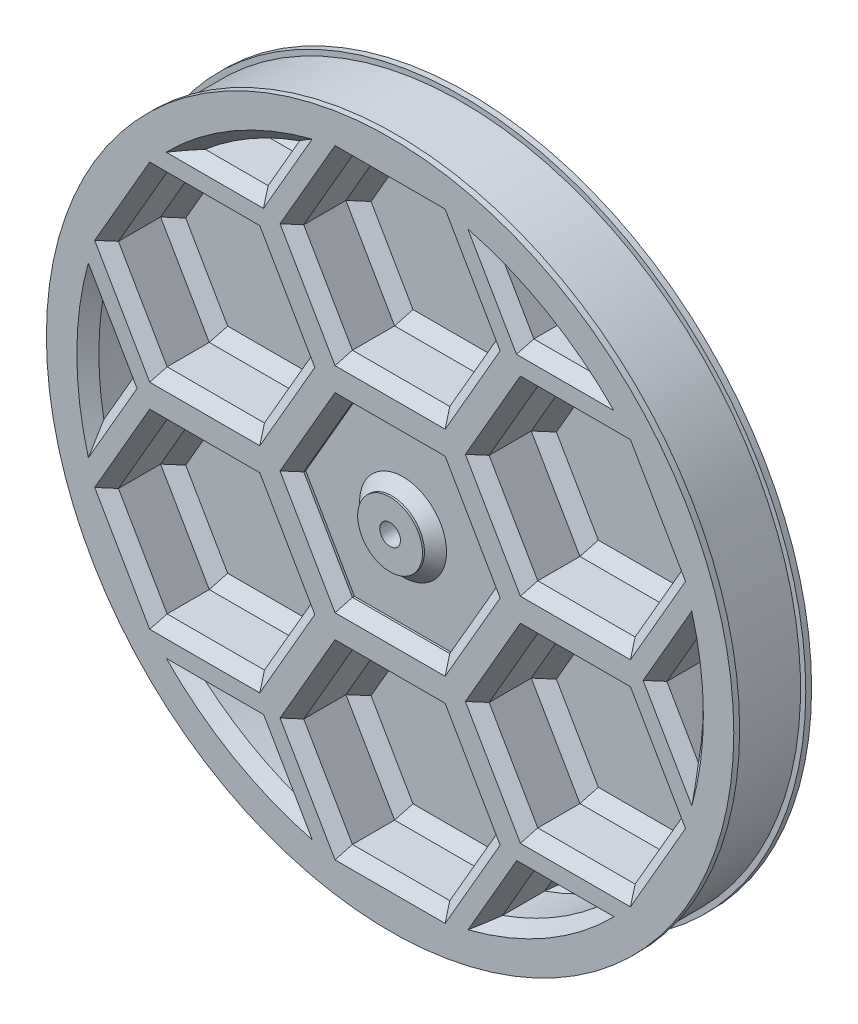
SolidWorks part; units mm, degrees
ref_plane "Front Plane" through (0, 0, 0) normal (0, 0, 1) x (1, 0, 0)
ref_plane "Top Plane" through (0, 0, 0) normal (0, 1, 0) x (1, 0, 0)
ref_plane "Right Plane" through (0, 0, 0) normal (1, 0, 0) x (0, 0, -1)
sketch "Sketch1" plane through (0, 0, 0) normal (0, 0, 1) x (1, 0, 0)
  circle A0 centre (0, 0) radius 33.655
  circle A1 centre (0, 0) radius 1.016
  dimension "D1" = 67.31
  dimension "D2" = 2.032
extrude "Boss-Extrude1" add sketch "Sketch1" along normal blind 7.62 contours A0 A1
sketch "Sketch2" plane through (0, 0, 7.62) normal (0, 0, 1) x (1, 0, 0)
  line L1 (9.5321, 20.955) -> (4.766, 29.21)
  line L2 (4.766, 29.21) -> (-4.766, 29.21)
  line L3 (-4.766, 29.21) -> (-9.5321, 20.955)
  line L4 (-9.5321, 20.955) -> (-4.766, 12.7)
  line L5 (-4.766, 12.7) -> (4.766, 12.7)
  line L6 (4.766, 12.7) -> (9.5321, 20.955)
  line L7 (-8.2562, 30.7849) -> (-13.0222, 39.0399)
  line L8 (-13.0222, 39.0399) -> (-22.5542, 39.0399)
  line L9 (-22.5542, 39.0399) -> (-27.3203, 30.7849)
  line L10 (-27.3203, 30.7849) -> (-22.5542, 22.5299)
  line L11 (-22.5542, 22.5299) -> (-13.0222, 22.5299)
  line L12 (-13.0222, 22.5299) -> (-8.2562, 30.7849)
  line L13 (-8.2416, 11.0999) -> (-13.0077, 19.3549) construction
  line L14 (-13.0077, 19.3549) -> (-22.5397, 19.3549) construction
  line L15 (-22.5397, 19.3549) -> (-27.3057, 11.0999) construction
  line L16 (-27.3057, 11.0999) -> (-22.5397, 2.8449) construction
  line L17 (-22.5397, 2.8449) -> (-13.0077, 2.8449) construction
  line L18 (-13.0077, 2.8449) -> (-8.2416, 11.0999) construction
  circle A0 centre (0, 0) radius 20.955 construction
  circle A1 centre (0, 20.955) radius 8.255 construction
  circle A2 centre (0, 20.955) radius 8.255 construction
  circle A3 centre (0, 0) radius 29.5963
  circle A4 centre (-17.7882, 30.7849) radius 8.255 construction
  circle A6 centre (-17.7737, 11.0999) radius 8.255 construction
  dimension "D1" = 41.91
  dimension "D2" = 16.51
  dimension "D3" = 3.81
  dimension "D4" = 3.81
  dimension "D5" = 3.175
extrude "Cut-Extrude1" cut sketch "Sketch2" against normal blind 6.35 contours L5 L6 L1 L2 L3 L4 | L12 A3 L11
pattern_circular "CirPattern1" count 6 over 360 about axis through (0, 0, 0) along (0, 0, 1) of "Cut-Extrude1"
sketch "Sketch3" plane through (0, 0, 7.62) normal (0, 0, 1) x (1, 0, 0)
  line L1 (9.5321, 0) -> (4.766, 8.255)
  line L2 (4.766, 8.255) -> (-4.766, 8.255)
  line L3 (-4.766, 8.255) -> (-9.5321, 0)
  line L4 (-9.5321, 0) -> (-4.766, -8.255)
  line L5 (-4.766, -8.255) -> (4.766, -8.255)
  line L6 (4.766, -8.255) -> (9.5321, 0)
  circle A0 centre (0, 0) radius 8.255 construction
  circle A1 centre (0, 0) radius 3.175
  dimension "D1" = 16.51
  dimension "D2" = 6.35
extrude "Cut-Extrude2" cut sketch "Sketch3" against normal blind 1.27
sketch "Sketch4" plane through (0, 0, 0) normal (1, 0, 0) x (0, 0, -1)
  line L0 (0, 33.655) -> (-7.62, 33.655) construction
  line L1 (-7.0485, 33.655) -> (-0.5715, 33.655)
  line L2 (-7.0485, 33.655) -> (-7.0485, 33.147)
  line L3 (-7.0485, 33.147) -> (-0.5715, 33.147)
  line L4 (-0.5715, 33.655) -> (-0.5715, 33.147)
  line L5 (-7.0485, 33.655) -> (-0.5715, 33.147) construction
  line L6 (-7.0485, 33.147) -> (-0.5715, 33.655) construction
  line L7 (0, 33.655) -> (-7.62, 33.655) construction
  point P4 (-3.81, 33.401)
  point P9 (-3.81, 33.655)
  dimension "D1" = 6.477
  dimension "D2" = 0.508
sketch "Sketch5" plane through (0, 0, 0) normal (1, 0, 0) x (0, 0, -1)
  line L0 (0, 0) -> (-29.2934, 0) construction
  line L1 (0, -33.655) -> (0, 33.655) construction
revolve "Cut-Revolve1" cut sketch "Sketch4" angle 360 about L0
chamfer "Chamfer1" distance 1.0795 angle 45 62 edges at (33.655, 0, 7.62) (-14.8065, 25.6263, 7.62) (-16.1072, 22.5299, 7.62) (-11.4779, 25.2047, 7.62) (7.149, 16.8275, 7.62) (7.149, 25.0825, 7.62) (0, 29.21, 7.62) (-7.149, 25.0825, 7.62) (-7.149, 16.8275, 7.62) (0, 12.7, 7.62) (-10.9985, 14.605, 7.62) (-18.1476, 18.7325, 7.62) (-25.2966, 14.605, 7.62) (-25.2966, 6.35, 7.62) (-18.1476, 2.2225, 7.62) (-10.9985, 6.35, 7.62) (14.8065, -25.6263, 7.62) (16.1072, -22.5299, 7.62) (11.4779, -25.2047, 7.62) (10.9985, -14.605, 7.62) (18.1476, -18.7325, 7.62) (25.2966, -14.605, 7.62) (25.2966, -6.35, 7.62) (18.1476, -2.2225, 7.62) (10.9985, -6.35, 7.62) (18.1476, 2.2225, 7.62) (25.2966, 6.35, 7.62) (25.2966, 14.605, 7.62) (18.1476, 18.7325, 7.62) (10.9985, 14.605, 7.62) (10.9985, 6.35, 7.62) (29.5963, 0.0097, 7.62) (27.5651, 2.6843, 7.62) (27.5668, -2.6622, 7.62) (-18.1476, -2.2225, 7.62) (-25.2966, -6.35, 7.62) (-25.2966, -14.605, 7.62) (-18.1476, -18.7325, 7.62) (-10.9985, -14.605, 7.62) (-10.9985, -6.35, 7.62) (-29.5963, -0.0097, 7.62) (-27.5651, -2.6843, 7.62) (-27.5668, 2.6622, 7.62) (-14.7897, -25.636, 7.62) (-11.4579, -25.2142, 7.62) (-16.0889, -22.5425, 7.62) (-7.149, -16.8275, 7.62) (-7.149, -25.0825, 7.62) (0, -29.21, 7.62) (7.149, -25.0825, 7.62) (7.149, -16.8275, 7.62) (0, -12.7, 7.62) (14.7897, 25.636, 7.62) (11.4579, 25.2142, 7.62) (16.0889, 22.5425, 7.62) (7.149, 4.1275, 7.62) (0, 8.255, 7.62) (-7.149, 4.1275, 7.62) (-7.149, -4.1275, 7.62) (0, -8.255, 7.62) (7.149, -4.1275, 7.62) (3.175, 0, 6.35)
sketch "Sketch6" plane through (0, 0, 0) normal (1, 0, 0) x (0, 0, -1)
  line L0 (0, 33.655) -> (-0.5715, 33.655) construction
  line L1 (-7.62, 33.655) -> (-7.0485, 33.655)
  line L2 (-7.62, 33.655) -> (-7.62, 32.385)
  line L3 (-7.62, 32.385) -> (-7.0485, 32.385)
  line L4 (-7.0485, 33.655) -> (-7.0485, 32.385)
  line L5 (-7.62, 33.655) -> (-7.0485, 32.385) construction
  line L6 (-7.62, 32.385) -> (-7.0485, 33.655) construction
  line L7 (0, 33.655) -> (-0.5715, 33.655) construction
  line L8 (-7.62, 32.5755) -> (-7.62, -32.5755) construction
  point P4 (-7.3342, 33.02)
  dimension "D1" = 1.27
revolve "Revolve1" add sketch "Sketch6" angle 360 about L0
chamfer "Chamfer2" distance 1.143 angle 45 54 edges at (-10.9985, -14.605, 1.27) (-18.1476, -18.7325, 1.27) (-25.2966, -14.605, 1.27) (-25.2966, -6.35, 1.27) (-18.1476, -2.2225, 1.27) (-10.9985, -6.35, 1.27) (-16.1072, 22.5299, 1.27) (-14.8065, 25.6263, 1.27) (-11.4779, 25.2047, 1.27) (11.4579, 25.2142, 1.27) (14.7897, 25.636, 1.27) (16.0889, 22.5425, 1.27) (-27.5651, -2.6843, 1.27) (-29.5963, -0.0097, 1.27) (-27.5668, 2.6622, 1.27) (-18.1476, 2.2225, 1.27) (-25.2966, 6.35, 1.27) (-25.2966, 14.605, 1.27) (-18.1476, 18.7325, 1.27) (-10.9985, 14.605, 1.27) (-10.9985, 6.35, 1.27) (-7.149, 16.8275, 1.27) (-7.149, 25.0825, 1.27) (0, 29.21, 1.27) (7.149, 25.0825, 1.27) (7.149, 16.8275, 1.27) (0, 12.7, 1.27) (10.9985, 14.605, 1.27) (18.1476, 18.7325, 1.27) (25.2966, 14.605, 1.27) (25.2966, 6.35, 1.27) (18.1476, 2.2225, 1.27) (10.9985, 6.35, 1.27) (27.5651, 2.6843, 1.27) (29.5963, 0.0097, 1.27) (27.5668, -2.6622, 1.27) (18.1476, -2.2225, 1.27) (25.2966, -6.35, 1.27) (25.2966, -14.605, 1.27) (18.1476, -18.7325, 1.27) (10.9985, -14.605, 1.27) (10.9985, -6.35, 1.27) (16.1072, -22.5299, 1.27) (14.8065, -25.6263, 1.27) (11.4779, -25.2047, 1.27) (7.149, -16.8275, 1.27) (7.149, -25.0825, 1.27) (0, -29.21, 1.27) (-7.149, -25.0825, 1.27) (-7.149, -16.8275, 1.27) (0, -12.7, 1.27) (-11.4579, -25.2142, 1.27) (-14.7897, -25.636, 1.27) (-16.0889, -22.5425, 1.27)
